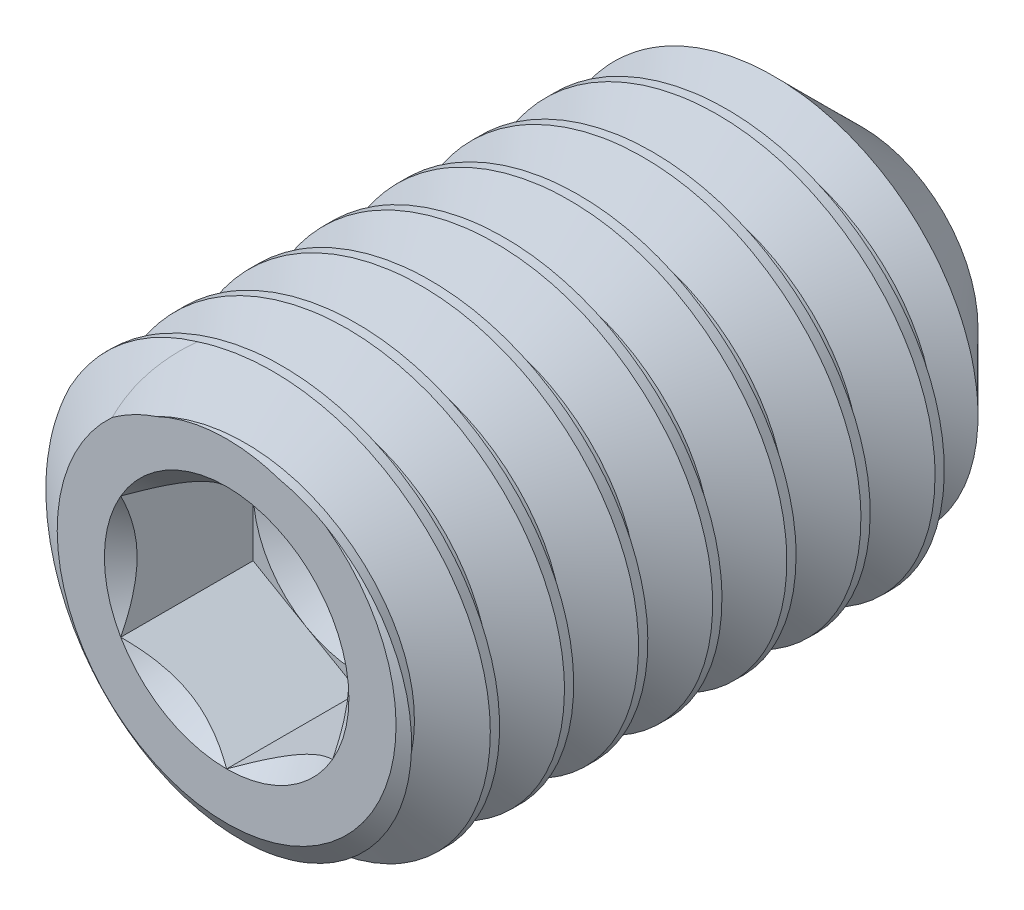
SolidWorks part; units mm, degrees
ref_plane "Front" through (0, 0, 0) normal (0, 0, 1) x (1, 0, 0)
ref_plane "Top" through (0, 0, 0) normal (0, 1, 0) x (1, 0, 0)
ref_plane "Right" through (0, 0, 0) normal (1, 0, 0) x (0, 0, -1)
sketch "Sketch22" plane through (0, 0, 0) normal (1, 0, 0) x (0, 0, -1)
  line L0 (-2.6707, 0) -> (-2.6707, 1.6)
  line L1 (-2.6707, 1.6) -> (-2.3907, 2)
  line L2 (-2.3907, 2) -> (2.4252, 2)
  line L3 (2.4252, 2) -> (3.3293, 1.0959)
  line L4 (3.3293, 1.0959) -> (2.6707, 0)
  line L5 (2.6707, 0) -> (-2.6707, 0)
  line L6 (2.6707, 0) -> (3.3293, 0) construction
  line L7 (3.3293, 0) -> (3.3293, 1.0959) construction
  line L8 (3.3293, -1.0959) -> (2.6707, 0) construction
  line L9 (-2.3907, -2) -> (2.4252, -2) construction
  dimension "Dia" = 4
  dimension "Length" = 6
  dimension "D3" = 35
  dimension "D5" = 118
  dimension "D6" = 45
  dimension "D7" = 3.2
revolve "Revolve1" add sketch "Sketch22" angle 360 about L6
ref_plane "Plane1" through (0, 0, -3.3293) normal (0, 0, 1) x (1, 0, 0)
sketch "Sketch27" plane through (0, 0, -3.3293) normal (0, 0, 1) x (1, 0, 0)
  circle A0 centre (0, 0) radius 2 construction
  circle A1 centre (0, 0) radius 2
curve "Helix/Spiral1" pitch 0.7 height 6.7 turns 9.5714
sketch "Sketch28" plane through (0, 0, 0) normal (1, 0, 0) x (0, 0, -1)
  line L0 (3.3293, 2) -> (3.9418, 2)
  line L1 (3.9418, 2) -> (3.6793, 1.5453)
  line L2 (3.6793, 1.5453) -> (3.5918, 1.5453)
  line L3 (3.5918, 1.5453) -> (3.3293, 2)
  line L4 (3.4605, 1.7727) -> (3.8105, 1.7727) construction
  line L6 (-2.3907, 2) -> (2.4252, 2) construction
  dimension "D1" = 0.0875
  dimension "D3" = 60
  dimension "D2" = 0.35
sweep "Cut-Sweep2" cut profiles "Sketch28" path "Helix/Spiral1"
sketch "Sketch23" plane through (0, 0, 2.6707) normal (0, 0, 1) x (1, 0, 0)
  line L1 (0, 1.1547) -> (-1, 0.5774)
  line L2 (-1, 0.5774) -> (-1, -0.5774)
  line L3 (-1, -0.5774) -> (0, -1.1547)
  line L4 (0, -1.1547) -> (1, -0.5774)
  line L5 (1, -0.5774) -> (1, 0.5774)
  line L6 (1, 0.5774) -> (0, 1.1547)
  circle A0 centre (0, 0) radius 1 construction
  dimension "Hex" = 2
extrude "Cut-Extrude10" cut sketch "Sketch23" against normal blind 1.25
sketch "Sketch24" plane through (0, 0, 2.6707) normal (0, 0, 1) x (1, 0, 0)
  circle A0 centre (0, 0) radius 1.1547
extrude "Cut-Extrude11" cut sketch "Sketch24" against normal through all draft 45
sketch "Sketch26" plane through (0, 0, 1.4207) normal (0, 0, 1) x (1, 0, 0)
  circle A0 centre (0, 0) radius 1 construction
  circle A1 centre (0, 0) radius 1
extrude "Cut-Extrude12" cut sketch "Sketch26" against normal through all draft 60
sketch "Sketch30" plane through (0, 0, 0) normal (1, 0, 0) x (0, 0, -1)
  line L0 (-2.3907, 2) -> (2.4252, 2) construction
  line L1 (-2.6707, 0) -> (-2.6707, 1.6) construction
  line L2 (3.3293, 0) -> (3.3293, 1.0959) construction
  line L3 (-2.3907, -2) -> (2.4252, -2) construction
  point P0 (-2.6707, 2)
  point P1 (3.3293, 2)
  point P2 (3.3293, -2)
  point P11 (2.2793, -2)
  dimension "D1" = 1.05
sketch "Sketch31" plane through (0, 0, 0) normal (1, 0, 0) x (0, 0, -1)
  line L2 (2.6707, 0) -> (3.3293, -1.0959)
  line L3 (3.3293, 1.0959) -> (2.6707, 0)
equation "\"D7@Sketch22\"=\"Dia@Sketch22\"*.8"
equation "\"D1@Sketch28\" = \"D4@Helix/Spiral1\" * .125"
equation "\"D2@Sketch28\" = \"D4@Helix/Spiral1\" * .5"
equation "\"D3@Helix/Spiral1\" = \"Length@Sketch22\" + \"D4@Helix/Spiral1\""
equation "\"D1@Sketch30\" = \"D4@Helix/Spiral1\" * 1.5"
equation "\"hex Depth@Cut-Extrude10\" = \"Hex@Sketch23\" * .625"
